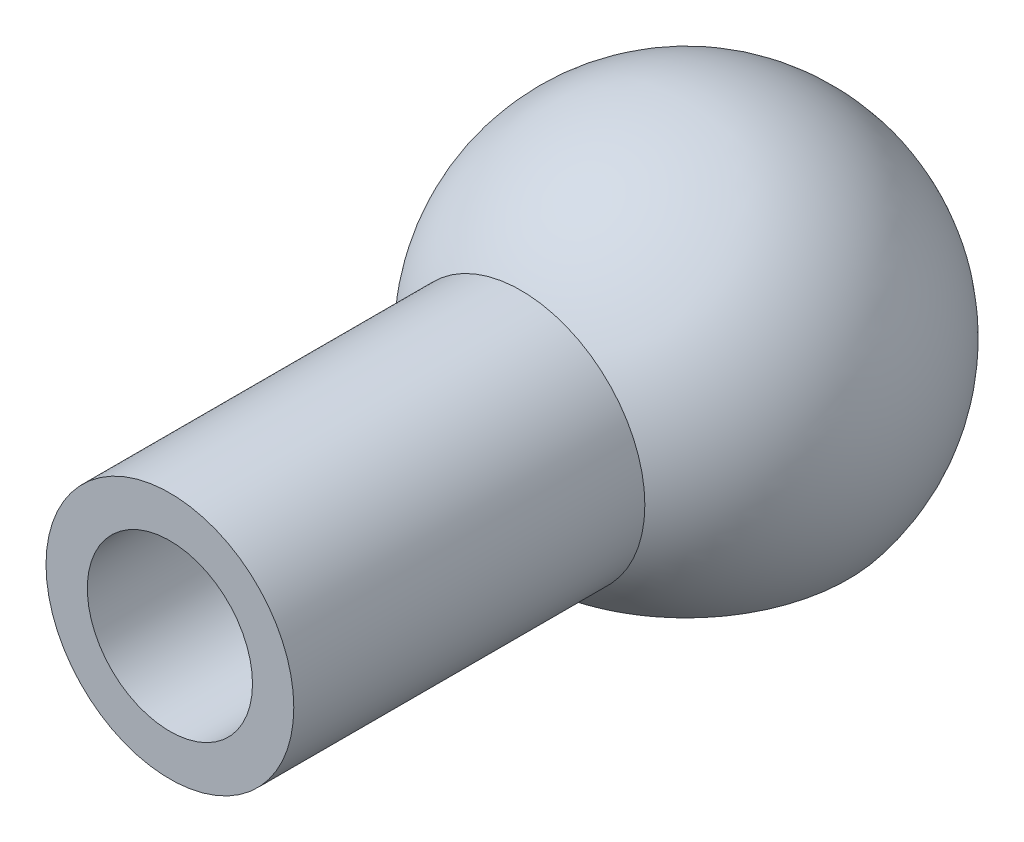
SolidWorks part; units mm, degrees
ref_plane "前视基准面" through (0, 0, 0) normal (0, 0, 1) x (1, 0, 0)
ref_plane "上视基准面" through (0, 0, 0) normal (0, 1, 0) x (1, 0, 0)
ref_plane "右视基准面" through (0, 0, 0) normal (1, 0, 0) x (0, 0, -1)
sketch "草图1" plane through (0, 0, 0) normal (0, 0, 1) x (1, 0, 0)
  circle A0 centre (0, 0) radius 6
  circle A1 centre (0, 0) radius 4
  dimension "D1" = 12
  dimension "D2" = 8
extrude "凸台-拉伸1" add sketch "草图1" along normal blind 25
sketch "草图2" plane through (0, 0, 0) normal (0, 1, 0) x (1, 0, 0)
  line L0 (0, 0) -> (0, 18.3774) construction
  line L1 (0, 10) -> (0, -10)
  arc A0 (0, 10) -> (0, -10) centre (0, 0) ccw
  dimension "D1" = 20
revolve "旋转3" add sketch "草图2" angle 360 about L0
sketch "草图3" plane through (0, 0, 25) normal (0, 0, 1) x (1, 0, 0)
  circle A0 centre (0, 0) radius 4
extrude "切除-拉伸2" cut sketch "草图3" against normal blind 17
sketch "草图4" plane through (0, 0, 0) normal (1, 0, 0) x (0, 0, -1)
  line L0 (0, 0) -> (0, 19.6414) construction
  line L1 (0, 7) -> (0, -7)
  line L2 (0, -7) -> (0, -10)
  line L3 (0, -10) -> (6, -10)
  line L5 (5.5, -4.3301) -> (7.8571, -6.1859)
  line L6 (7.8571, -6.1859) -> (6, -10)
  arc A0 (0, 7) -> (5.5, -4.3301) centre (0, 0) cw
  arc A1 (-8, -6) -> (-8, 6) centre (0, 0) ccw construction
  dimension "D1" = 7
  dimension "D2" = 3
  dimension "D3" = 5.5
revolve "切除-旋转1" cut sketch "草图4" angle 360 about L0
